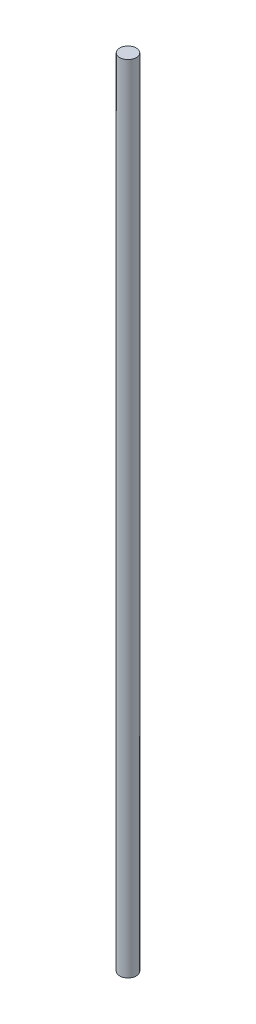
SolidWorks part; units mm, degrees
ref_plane "Front Plane" through (0, 0, 0) normal (0, 0, 1) x (1, 0, 0)
ref_plane "Top Plane" through (0, 0, 0) normal (0, 1, 0) x (1, 0, 0)
ref_plane "Right Plane" through (0, 0, 0) normal (1, 0, 0) x (0, 0, -1)
sketch "Sketch1" plane through (0, 0, 0) normal (0, 1, 0) x (1, 0, 0)
  circle A0 centre (0, 0) radius 6.35
  dimension "D1" = 12.7
extrude "Boss-Extrude1" add sketch "Sketch1" along normal mid plane 606.552
